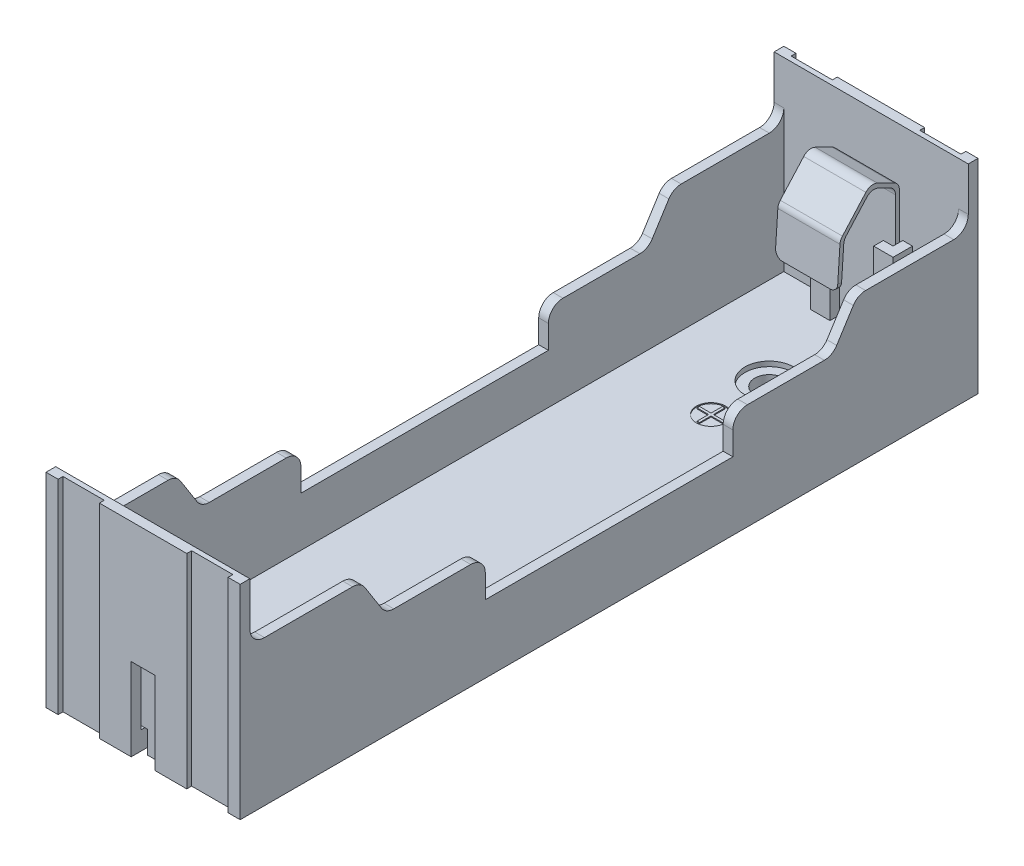
SolidWorks part; units mm, degrees
material "ABS"
ref_plane "Спереди" through (0, 0, 0) normal (0, 0, 1) x (1, 0, 0)
ref_plane "Сверху" through (0, 0, 0) normal (0, 1, 0) x (1, 0, 0)
ref_plane "Справа" through (0, 0, 0) normal (1, 0, 0) x (0, 0, -1)
other "Configuration Table"
sketch "Эскиз1" plane through (0, 0, 0) normal (0, 1, 0) x (1, 0, 0)
  line L1 (-10, 38) -> (10, 38)
  line L2 (-10, 38) -> (-10, -38)
  line L3 (-10, -38) -> (10, -38)
  line L4 (10, 38) -> (10, -38)
  line L5 (-10, 38) -> (10, -38) construction
  line L6 (-10, -38) -> (10, 38) construction
  point P0 (0, 0)
  dimension "D1" = 76
  dimension "D2" = 20
extrude "Основа" add sketch "Эскиз1" along normal blind 21
sketch "Эскиз2" plane through (0, 0, 0) normal (0, 1, 0) x (1, 0, 0)
  line L1 (10, 38) -> (-10, 38) construction
  line L2 (-4.5, 38) -> (-4.5, 37.5)
  line L3 (-4.5, 37.5) -> (-8.75, 37.5)
  line L4 (-8.75, 37.5) -> (-8.75, 38)
  line L5 (-8.75, 38) -> (-10.75, 38)
  line L6 (-10.75, 38) -> (-10.75, 37.5)
  line L13 (-10.75, 38) -> (-10, 38)
  line L14 (-10, 38) -> (-10, 46.5071)
  line L15 (-10, 46.5071) -> (10, 46.5071)
  line L16 (0, 46.5071) -> (0, 38)
  line L17 (4.5, 38) -> (-4.5, 38)
  line L18 (10, 38) -> (10, 46.5071)
  line L26 (10.75, 38) -> (10.75, 37.5)
  line L27 (8.75, 38) -> (10.75, 38)
  line L28 (4.5, 38) -> (4.5, 37.5)
  line L29 (4.5, 37.5) -> (8.75, 37.5)
  line L30 (8.75, 37.5) -> (8.75, 38)
  line L31 (10.75, 38) -> (10, 38)
  line L32 (-10.75, 37.5) -> (-8.75, 37.5)
  line L33 (10.75, 37.5) -> (8.75, 37.5)
  point P22 (0, 38)
  dimension "D1" = 9
  dimension "D2" = 2
  dimension "D3" = 4.25
  dimension "D4" = 0.5
extrude "Рёбра" cut sketch "Эскиз2" along normal through all contours L29 L30 L27 L26 L18 L15 L16 L17 L28 | L17 L16 L15 L14 L13 L6 L5 L4 L3 L2 region at (-5.0396, 0, -42.1438) region at (5.0396, 0, -42.1438)
mirror "Зеркальное отражение1" about plane through (0, 0, 0) normal (0, 0, 1) of "Рёбра"
sketch "Эскиз3" plane through (0, 21, 0) normal (0, 1, 0) x (1, 0, 0)
  line L0 (9, 0) -> (-9, 0) construction
  line L1 (9, 37) -> (-9, 37)
  line L2 (9, 37) -> (9, -37)
  line L3 (9, -37) -> (-9, -37)
  line L4 (-9, 37) -> (-9, -37)
  line L5 (9, 37) -> (-9, -37) construction
  line L6 (9, -37) -> (-9, 37) construction
  point P0 (0, 0)
  point P9 (0, 0)
  dimension "D1" = 18
  dimension "D2" = 74
extrude "Отсеки" cut sketch "Эскиз3" against normal blind 19.1
sketch "Эскиз4" plane through (0, 0, 0) normal (1, 0, 0) x (0, 0, -1)
  line L0 (37, 21) -> (-37, 21) construction
  line L1 (37, 27) -> (-37, 27)
  line L2 (37, 27) -> (37, 15)
  line L3 (37, 15) -> (-37, 15)
  line L4 (-37, 27) -> (-37, 15)
  line L5 (37, 27) -> (-37, 15) construction
  line L6 (37, 15) -> (-37, 27) construction
  line L7 (-37, 1.9) -> (-37, 21) construction
  point P0 (0, 21)
  dimension "D1" = 15
extrude "Уменьшение внутренних стенок" cut sketch "Эскиз4" against normal blind 15 and the other way blind 15
sketch "Эскиз5" plane through (10, 0, 0) normal (1, 0, 0) x (0, 0, -1)
  line L0 (-38, 21) -> (-35.6, 21)
  line L1 (-38, 21) -> (-37, 21) construction
  line L2 (-35.6, 21) -> (-35.6, 15)
  line L3 (-35.6, 15) -> (-25.6, 15)
  line L4 (-25.6, 15) -> (-23, 10.9)
  line L5 (-23, 10.9) -> (-12.75, 10.9)
  line L6 (-12.75, 10.9) -> (-12.75, 7)
  line L7 (-12.75, 7) -> (12.75, 7)
  line L8 (0, 7) -> (0, 0) construction
  line L9 (-35.6, 21) -> (35.6, 21)
  line L10 (12.75, 10.9) -> (12.75, 7)
  line L11 (23, 10.9) -> (12.75, 10.9)
  line L12 (25.6, 15) -> (23, 10.9)
  line L13 (35.6, 15) -> (25.6, 15)
  line L14 (35.6, 21) -> (35.6, 15)
  line L15 (-38, 21) -> (-37, 21) construction
  point P20 (0, 21)
  line M12 (38, 21) -> (37, 21)
  dimension "D1" = 12.75
  dimension "D2" = 10.25
  dimension "D3" = 2.4
  dimension "D4" = 10
  dimension "D5" = 6
  dimension "D6" = 3.9
  dimension "D7" = 7
extrude "Уменьшение внешних стенок" cut sketch "Эскиз5" against normal blind 15 contours L14 L2 L3 L4 L5 L6 L7 L10 L11 L12 L13 M12 region at (10, 15.384, 0)
fillet "Скругление2" radius 1.5 8 edges at (9.5, 10.9, -23) (9.5, 10.9, -12.75) (9.5, 10.9, 12.75) (9.5, 10.9, 23) (9.5, 15, -37) (9.5, 15, -25.6) (9.5, 15, 37) (9.5, 15, 25.6)
mirror "Зеркальное отражение2" about plane through (0, 0, 0) normal (1, 0, 0) of "Скругление2", "Уменьшение внешних стенок"
sketch "Эскиз6" plane through (0, 0, 0) normal (0, 1, 0) x (1, 0, 0)
  line L0 (-4.5, -38) -> (4.5, -38) construction
  line L1 (-1.225, -41.5) -> (1.225, -41.5)
  line L2 (-1.225, -41.5) -> (-1.225, -34.5)
  line L3 (-1.225, -34.5) -> (1.225, -34.5)
  line L4 (1.225, -41.5) -> (1.225, -34.5)
  line L5 (-1.225, -41.5) -> (1.225, -34.5) construction
  line L6 (-1.225, -34.5) -> (1.225, -41.5) construction
  line L7 (-10, 0) -> (10, 0) construction
  line L8 (10, -38) -> (10, 38) construction
  line L27 (-1.225, 34.5) -> (1.225, 41.5) construction
  line L28 (-1.225, 41.5) -> (1.225, 34.5) construction
  line L37 (1.225, 41.5) -> (1.225, 34.5)
  line L38 (-1.225, 34.5) -> (1.225, 34.5)
  line L39 (-1.225, 41.5) -> (-1.225, 34.5)
  line L40 (-1.225, 41.5) -> (1.225, 41.5)
  point P0 (0, -38)
  point P13 (0, 0)
  point P42 (0, 38)
  dimension "D1" = 2.45
  dimension "D2" = 3.5
extrude "Вырезы под контакты" cut sketch "Эскиз6" along normal blind 8.5
sketch "Эскиз11" plane through (0, 0, 0) normal (0, 1, 0) x (1, 0, 0)
  line L0 (0, 26.5) -> (0, -26.5) construction
  line L1 (1.5, -26.5) -> (-1.5, -26.5) construction
  line L3 (1.5, 26.5) -> (-1.5, 26.5) construction
  line L4 (4.5, 38) -> (-4.5, 38) construction
  line L5 (0, 28) -> (0, 25) construction
  line L6 (0, -25) -> (0, -28) construction
  line L7 (-4.5, -38) -> (4.5, -38) construction
  circle A1 centre (0, 26.5) radius 1.5
  circle A4 centre (0, -26.5) radius 1.5
  point P0 (0, 0)
  point P13 (0, 0)
  dimension "D2" = 3
  dimension "D3" = 11.5
  dimension "D5" = 10
  dimension "D1" = 53
  dimension "D4" = 10
extrude "Крепежные отверстия" cut sketch "Эскиз11" along normal through all
sketch "Эскиз12" plane through (0, 0, 0) normal (0, 1, 0) x (1, 0, 0)
  circle A1 centre (0, 26.5) radius 1.5 construction
  circle A4 centre (0, -26.5) radius 1.5 construction
  circle A7 centre (0, 26.5) radius 1.5
  circle A10 centre (0, -26.5) radius 1.5
  circle A13 centre (0, 26.5) radius 2.8
  circle A16 centre (0, -26.5) radius 2.8
  dimension "D1" = 1.3
extrude "Юбки отверстий" add sketch "Эскиз12" against normal blind 0.3
sketch "Эскиз13" plane through (0, 1.9, 0) normal (0, 1, 0) x (1, 0, 0)
  circle A1 centre (0, -26.5) radius 1.5 construction
  circle A3 centre (0, 26.5) radius 1.5 construction
  circle A6 centre (0, -26.5) radius 1.5
  circle A8 centre (0, 26.5) radius 1.5
  circle A13 centre (0, -26.5) radius 2.5
  circle A15 centre (0, 26.5) radius 2.5
  dimension "D1" = 1
extrude "Вырез-Вытянуть17" cut sketch "Эскиз13" against normal blind 0.5
sketch "Эскиз14" plane through (0, 1.9, 0) normal (0, 1, 0) x (1, 0, 0)
  line L0 (0, 20.5) -> (0, -20.5) construction
  line L3 (1.5, 20.5) -> (0, 20.5) construction
  line L4 (0, -20.5) -> (0, -19) construction
  line L5 (0, 19) -> (0, 20.5) construction
  line L8 (0.125, -19.2) -> (-0.125, -19.2)
  line L9 (0.125, -19.2) -> (0.125, -21.8)
  line L10 (0.125, -21.8) -> (-0.125, -21.8)
  line L11 (-0.125, -19.2) -> (-0.125, -21.8)
  line L12 (0.125, -19.2) -> (-0.125, -21.8) construction
  line L13 (0.125, -21.8) -> (-0.125, -19.2) construction
  line L14 (0.125, 21.8) -> (-0.125, 21.8)
  line L15 (0.125, 21.8) -> (0.125, 19.2)
  line L16 (0.125, 19.2) -> (-0.125, 19.2)
  line L17 (-0.125, 21.8) -> (-0.125, 19.2)
  line L18 (0.125, 21.8) -> (-0.125, 19.2) construction
  line L19 (0.125, 19.2) -> (-0.125, 21.8) construction
  line L20 (1.3, 20.625) -> (-1.3, 20.625)
  line L21 (1.3, 20.625) -> (1.3, 20.375)
  line L22 (1.3, 20.375) -> (-1.3, 20.375)
  line L23 (-1.3, 20.625) -> (-1.3, 20.375)
  line L24 (1.3, 20.625) -> (-1.3, 20.375) construction
  line L25 (1.3, 20.375) -> (-1.3, 20.625) construction
  circle A0 centre (0, 20.5) radius 1.5
  circle A1 centre (0, -20.5) radius 1.5
  point P0 (0, 0)
  point P2 (0, 0)
  dimension "D2" = 3
  dimension "D3" = 2.6
  dimension "D4" = 0.25
  dimension "D5" = 41
extrude "Полярность" cut sketch "Эскиз14" against normal blind 0.1 contours A1 L11 L8 L9 L10 | A0 L23 L20 L17 L14 L15 L21 L22 L16 region at (-1.4576, 1.9, -20.5) region at (-1.4576, 1.9, 20.5)
sketch "Эскиз15" plane through (0, 1.9, 0) normal (0, 1, 0) x (1, 0, 0)
  line L0 (-1.225, 37) -> (-9, 37) construction
  line L1 (-1.225, 37) -> (-1.225, 34.5) construction
  line L16 (-2.25, 35) -> (-4.25, 35)
  line L17 (-4.25, 35) -> (-4.25, 37)
  line L18 (-4.25, 37) -> (-3.25, 37)
  line L19 (-3.25, 37) -> (-3.25, 36)
  line L20 (-3.25, 36) -> (-2.25, 36)
  line L21 (-2.25, 36) -> (-2.25, 35)
  line L22 (2.25, 35) -> (2.25, 36)
  line L23 (2.25, 36) -> (3.25, 36)
  line L24 (3.25, 36) -> (3.25, 37)
  line L25 (3.25, 37) -> (4.25, 37)
  line L26 (4.25, 37) -> (4.25, 35)
  line L27 (4.25, 35) -> (2.25, 35)
  line L28 (0, 35.5) -> (0, 35) construction
  line L29 (-2.25, 35) -> (2.25, 35) construction
  line L44 (10, 0) -> (-10, 0) construction
  line L45 (-10, -12.75) -> (-10, 12.75) construction
  line L48 (-2.25, -35) -> (2.25, -35) construction
  line L49 (0, -35.5) -> (0, -35) construction
  line L64 (4.25, -35) -> (2.25, -35)
  line L65 (4.25, -37) -> (4.25, -35)
  line L66 (3.25, -37) -> (4.25, -37)
  line L67 (3.25, -36) -> (3.25, -37)
  line L68 (2.25, -36) -> (3.25, -36)
  line L69 (2.25, -35) -> (2.25, -36)
  line L70 (-2.25, -36) -> (-2.25, -35)
  line L71 (-3.25, -36) -> (-2.25, -36)
  line L72 (-3.25, -37) -> (-3.25, -36)
  line L73 (-4.25, -37) -> (-3.25, -37)
  line L74 (-4.25, -35) -> (-4.25, -37)
  line L75 (-2.25, -35) -> (-4.25, -35)
  point P4 (19.5, 35)
  point P24 (0, 35)
  point P55 (0, 0)
  point P99 (0, -35)
  dimension "D1" = 2
  dimension "D2" = 1.025
  dimension "D4" = 8.5
extrude "Пазы для контактов" add sketch "Эскиз15" along normal blind 8.9
ref_plane "Для эскиза контактов" through (0, 0, 0) normal (-1, 0, 0) x (0, 0, 1)
sketch "Эскиз16" plane through (0, 0, 0) normal (-1, 0, 0) x (0, 0, 1)
  line L1 (-38, 21) -> (-38, 0) construction
  line L3 (-36.5, 17.26) -> (-36.5, 15.9523) construction
  line L4 (-36.5, 15.9523) -> (-33.8, 17.26)
  line L5 (-33.8, 17.26) -> (-30.8, 13.9059)
  line L6 (-30.8, 13.9059) -> (-30.5, 9.4159)
  line L7 (-36.5, 17.26) -> (-33.8, 17.26) construction
  line L8 (-36.5, 15.9523) -> (-36.5, 2)
  line L10 (-36.5, 2) -> (-36.5, -3.54) construction
  line L12 (-38, 0) -> (38, 0) construction
  dimension "D1" = 20.8
  dimension "D2" = 3
  dimension "D3" = 4.5
  dimension "D4" = 6
  dimension "D5" = 5.7
  dimension "D6" = 2.7
  dimension "D7" = 2
  dimension "D8" = 1.5
  dimension "D9" = 13.9523
extrude "Контакт" add sketch "Эскиз16" along normal mid plane 6.4 thin thin type mid plane wall 0.4
sketch "Эскиз17" plane through (0, 2, 0) normal (0, -1, 0) x (1, 0, 0)
  line L0 (0, -36.7) -> (0, -36.3) construction
  line L1 (-3.2, -36.7) -> (3.2, -36.7) construction
  line L2 (-3.2, -36.3) -> (3.2, -36.3) construction
  line L4 (0.85, -36.3) -> (-0.85, -36.3)
  line L5 (0.85, -36.3) -> (0.85, -36.7)
  line L6 (0.85, -36.7) -> (-0.85, -36.7)
  line L7 (-0.85, -36.3) -> (-0.85, -36.7)
  line L8 (0.85, -36.3) -> (-0.85, -36.7) construction
  line L9 (0.85, -36.7) -> (-0.85, -36.3) construction
  point P6 (0, -36.5)
  dimension "D1" = 1.7
extrude "Штырёк для пайки" add sketch "Эскиз17" along normal blind 5.5
fillet "Скругление3" radius 1 6 edges at (0, 13.8239, -30.995) (0, 13.9879, -30.605) (0, 17.0143, -33.8485) (0, 17.5057, -33.7515) (0, 15.827, -36.3) (0, 16.0777, -36.7)
fillet "Скругление4" radius 0.75 6 edges at (3.2, 2, -36.5) (0.85, -3.5, -36.5) (-0.85, -3.5, -36.5) (-3.2, 2, -36.5) (3.2, 9.4159, -30.5) (-3.2, 9.4159, -30.5)
mirror "Mirror1" about plane through (0, 0, 0) normal (0, 0, 1) of bodies 125
sketch "Эскиз18" plane through (0, 0, 38) normal (0, 0, 1) x (1, 0, 0)
  line L0 (-0.85, -2.75) -> (-0.85, 2) construction
  line L1 (-0.85, -0.3106) -> (0.9335, -0.3106)
  line L2 (-0.85, -0.3106) -> (-0.85, -3.6416)
  line L3 (-0.85, -3.6416) -> (0.9335, -3.6416)
  line L4 (0.9335, -0.3106) -> (0.9335, -3.6416)
extrude "Вырез-Вытянуть18" cut sketch "Эскиз18" against normal through all
equation "\"D1@Эскиз5\"=25.5/2"
